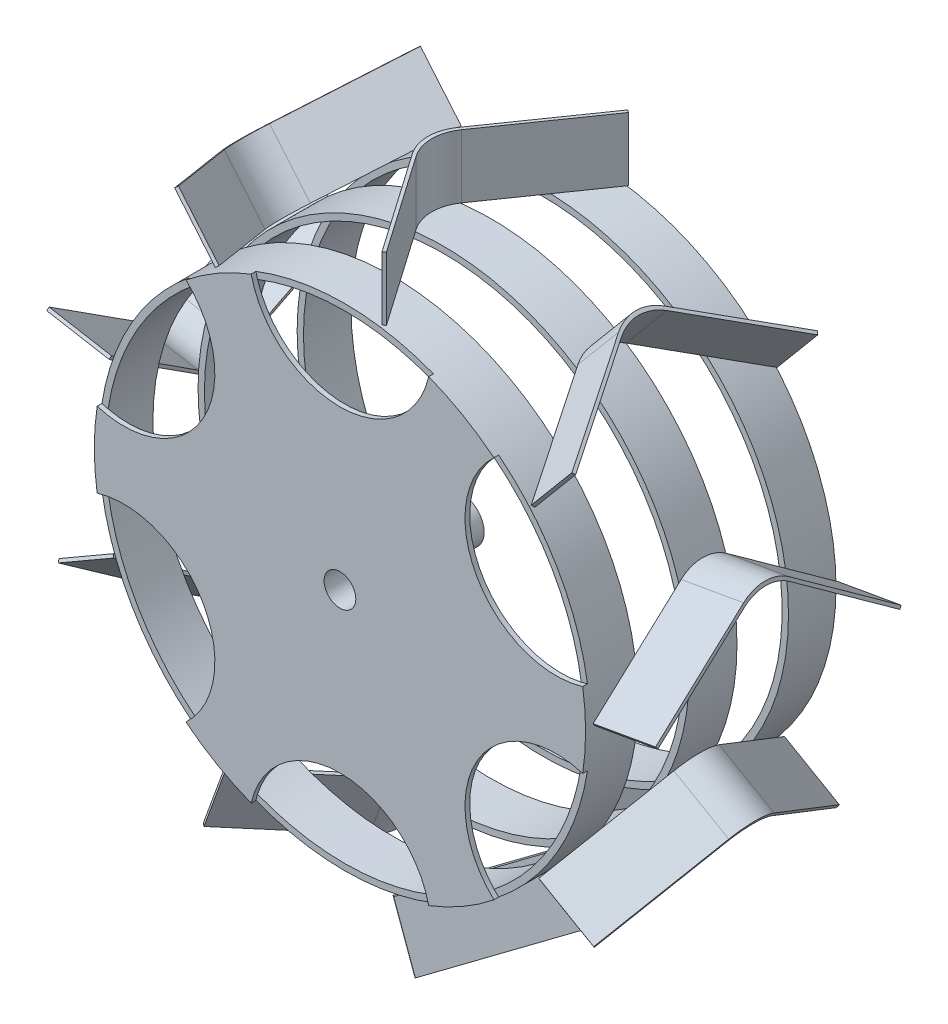
SolidWorks part; units mm, degrees
other "Папка сварных швов"
ref_plane "Спереди" through (0, 0, 0) normal (0, 0, 1) x (1, 0, 0)
ref_plane "Сверху" through (0, 0, 0) normal (0, 1, 0) x (1, 0, 0)
ref_plane "Справа" through (0, 0, 0) normal (1, 0, 0) x (0, 0, -1)
sketch "Эскиз1" plane through (0, 0, 0) normal (0, 0, 1) x (1, 0, 0)
  arc A0 (-56.0167, 144.5238) -> (-97.153, 120.7738) centre (0, 0) ccw
  arc A1 (-56.0167, 144.5238) -> (56.0167, 144.5238) centre (0, 157.5) ccw
  arc A2 (97.153, 120.7738) -> (153.1696, 23.75) centre (136.399, 78.75) ccw
  arc A3 (153.1696, -23.75) -> (97.153, -120.7738) centre (136.399, -78.75) ccw
  arc A4 (56.0167, -144.5238) -> (-56.0167, -144.5238) centre (0, -157.5) ccw
  arc A5 (-97.153, -120.7738) -> (-153.1696, -23.75) centre (-136.399, -78.75) ccw
  arc A6 (-153.1696, 23.75) -> (-97.153, 120.7738) centre (-136.399, 78.75) ccw
  arc A7 (97.153, 120.7738) -> (56.0167, 144.5238) centre (0, 0) ccw
  arc A8 (-153.1696, 23.75) -> (-153.1696, -23.75) centre (0, 0) ccw
  arc A9 (-97.153, -120.7738) -> (-56.0167, -144.5238) centre (0, 0) ccw
  arc A10 (56.0167, -144.5238) -> (97.153, -120.7738) centre (0, 0) ccw
  arc A11 (153.1696, -23.75) -> (153.1696, 23.75) centre (0, 0) ccw
  point P23 (0, 0)
  dimension "D1" = 310
  dimension "D2" = 115
  dimension "D3" = 100
  dimension "D4" = 6
extrude "Бобышка-Вытянуть1" add sketch "Эскиз1" against normal blind 3
sketch "Эскиз2" plane through (0, 0, -3) normal (0, 0, -1) x (-1, 0, 0)
  circle A0 centre (0, 0) radius 14
  circle A1 centre (0, 0) radius 10
  dimension "D1" = 28
  dimension "D2" = 20
extrude "Вырез-Вытянуть1" cut sketch "Эскиз2" against normal blind 3 contours A0
extrude "Бобышка-Вытянуть2" add sketch "Эскиз2<4>" along normal blind 74 and the other way blind 3
sketch "Эскиз2<4>" plane through (0, 0, -3) normal (0, 0, -1) x (-1, 0, 0) same geometry as "Эскиз2"
sketch "Эскиз4" plane through (0, 0, 0) normal (0, 1, 0) x (1, 0, 0)
  line L0 (14, 77) -> (-14, 77) construction
  circle A0 centre (0, 56.5) radius 4
  dimension "D1" = 8
  dimension "D2" = 16.5
extrude "Вырез-Вытянуть2" cut sketch "Эскиз4" against normal up to next and the other way up to next
sketch "Эскиз5" plane through (0, 0, -3) normal (0, 0, -1) x (-1, 0, 0)
  circle A0 centre (0, 0) radius 155
  circle A1 centre (0, 0) radius 151
  dimension "D1" = 310
  dimension "D2" = 4
extrude "Бобышка-Вытянуть3" add sketch "Эскиз5" along normal blind 30
ref_plane "Плоскость1" through (0, 0, -80.5) normal (0, 0, -1) x (-1, 0, 0)
ref_plane "Плоскость2" through (0, 0, -128) normal (0, 0, -1) x (-1, 0, 0)
sketch "Эскиз6" plane through (0, 0, -128) normal (0, 0, -1) x (-1, 0, 0)
  circle A0 centre (0, 0) radius 155
  circle A1 centre (0, 0) radius 151
  dimension "D1" = 310
  dimension "D2" = 4
sketch "Эскиз7" plane through (0, 0, -80.5) normal (0, 0, -1) x (-1, 0, 0)
  circle A0 centre (0, 0) radius 155
  circle A1 centre (0, 0) radius 151
  dimension "D1" = 310
  dimension "D2" = 4
extrude "Бобышка-Вытянуть4" add sketch "Эскиз7" along normal blind 15 and the other way blind 15 separate body
extrude "Бобышка-Вытянуть5" add sketch "Эскиз6" along normal blind 30 separate body
ref_plane "Плоскость3" through (0, 155, 0) normal (0, 1, 0) x (1, 0, 0)
sketch "Эскиз9" plane through (0, 155, 0) normal (0, 1, 0) x (1, 0, 0)
  line L0 (23.5298, 158) -> (-20.5118, 94.7921)
  line L1 (-155, 80.5) -> (183.1304, 80.5) construction
  line L2 (-20.5118, 66.2079) -> (23.5298, 3)
  line L3 (155, 158) -> (-155, 158) construction
  line L4 (-25, 80.5) -> (25.1707, 80.5) construction
  line L5 (-56.0167, 3) -> (56.0167, 3) construction
  line L6 (25.1707, 156.8566) -> (-18.0742, 94.7921)
  line L7 (-18.0742, 66.2079) -> (25.1707, 4.1434)
  line L8 (25.1707, 156.8566) -> (23.5298, 158)
  line L9 (25.1707, 4.1434) -> (23.5298, 3)
  line L10 (-155, 95.5) -> (-155, 65.5) construction
  arc A0 (-18.0742, 94.7921) -> (-18.0742, 66.2079) centre (2.4376, 80.5) ccw
  arc A1 (-20.5118, 94.7921) -> (-20.5118, 66.2079) centre (0, 80.5) ccw
  point P20 (-30.4702, 80.5)
  dimension "D3" = 25
  dimension "D1" = 54
  dimension "D4" = 2
  dimension "D2" = 2
extrude "Бобышка-Вытянуть6" add sketch "Эскиз9" along normal blind 40 separate body
pattern_circular "Круговой массив5" count 9 over 360 about axis through (0, 0, 0) along (0, 0, -1) of bodies 110
